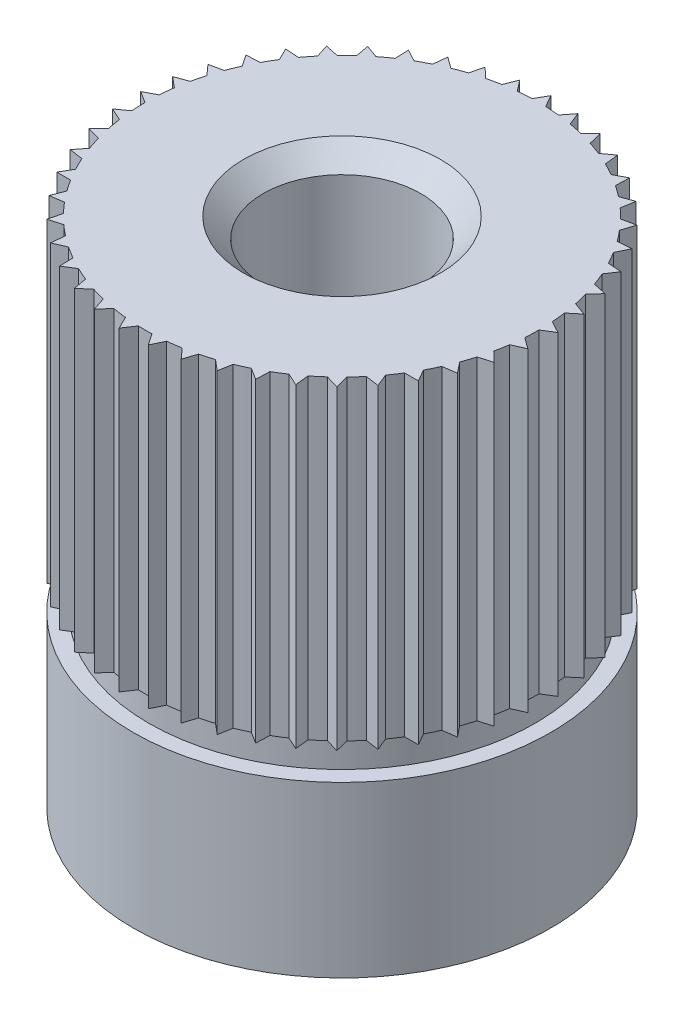
SolidWorks part; units mm, degrees
ref_plane "Piano frontale" through (0, 0, 0) normal (0, 0, 1) x (1, 0, 0)
ref_plane "Piano superiore" through (0, 0, 0) normal (0, 1, 0) x (1, 0, 0)
ref_plane "Piano destro" through (0, 0, 0) normal (1, 0, 0) x (0, 0, -1)
sketch "Schizzo1" plane through (0, 0, 0) normal (0, 1, 0) x (1, 0, 0)
  circle A0 centre (0, 0) radius 2.65
  dimension "D1" = 5.3
extrude "Estrusione-Estrusione1" add sketch "Schizzo1" along normal blind 2.15
sketch "Schizzo2" plane through (0, 2.15, 0) normal (0, 1, 0) x (1, 0, 0)
  circle A2 centre (0, 0) radius 2.55
  circle A3 centre (0, 0) radius 2.55
  dimension "D1" = 0.1
extrude "Estrusione-Estrusione2" add sketch "Schizzo2" along normal blind 0.35
sketch "Schizzo3" plane through (0, 2.5, 0) normal (0, 1, 0) x (1, 0, 0)
  line L0 (0, 2.8516) -> (0, -2.8947) construction
  line L1 (0, 2.65) -> (-0.0875, 2.4985)
  line L2 (0, 2.65) -> (0.0875, 2.4985)
  circle A2 centre (0, 0) radius 2.65 construction
  circle A3 centre (0, 0) radius 2.5
  arc A4 (0.0875, 2.4985) -> (-0.0875, 2.4985) centre (0, 0) ccw
  circle A5 centre (0, 0) radius 2.65 construction
  dimension "D2" = 30
  dimension "D3" = 30
  dimension "D1" = 0.05
extrude "Estrusione-Estrusione3" add sketch "Schizzo3" along normal blind 4
sketch "Schizzo4" plane through (0, 2.5, 0) normal (0, 1, 0) x (1, 0, 0)
  circle A0 centre (0, 0) radius 2.5
extrude "Estrusione-Estrusione4" add sketch "Schizzo4" along normal blind 4
ref_axis "Assi1" through (0, 6.5, 0) along (0, -1, 0)
pattern_circular "RipetizioneCircolare1" count 45 over 360 about axis through (0, 6.5, 0) along (0, -1, 0) of "Estrusione-Estrusione3"
sketch "Schizzo5" plane through (0, 6.5, 0) normal (0, 1, 0) x (1, 0, 0)
  circle A0 centre (0, 0) radius 1
  dimension "D1" = 2
extrude "Taglio-Estrusione1" cut sketch "Schizzo5" against normal through all
chamfer "Smusso1" distance 0.25 angle 45 1 edges at (0, 6.5, 1)
sketch "Schizzo6" plane through (0, 2.15, 0) normal (0, 1, 0) x (1, 0, 0)
  circle A2 centre (0, 0) radius 2.45
  circle A3 centre (0, 0) radius 2.45
  circle A5 centre (0, 0) radius 2.75
  circle A6 centre (0, 0) radius 2.75
  dimension "D1" = 0.1
  dimension "D2" = 0.1
extrude "Taglio-Estrusione2" cut sketch "Schizzo6" along normal up to surface (0.35 mm away) up to face at (-1.0266, 2.5, 2.3057)
